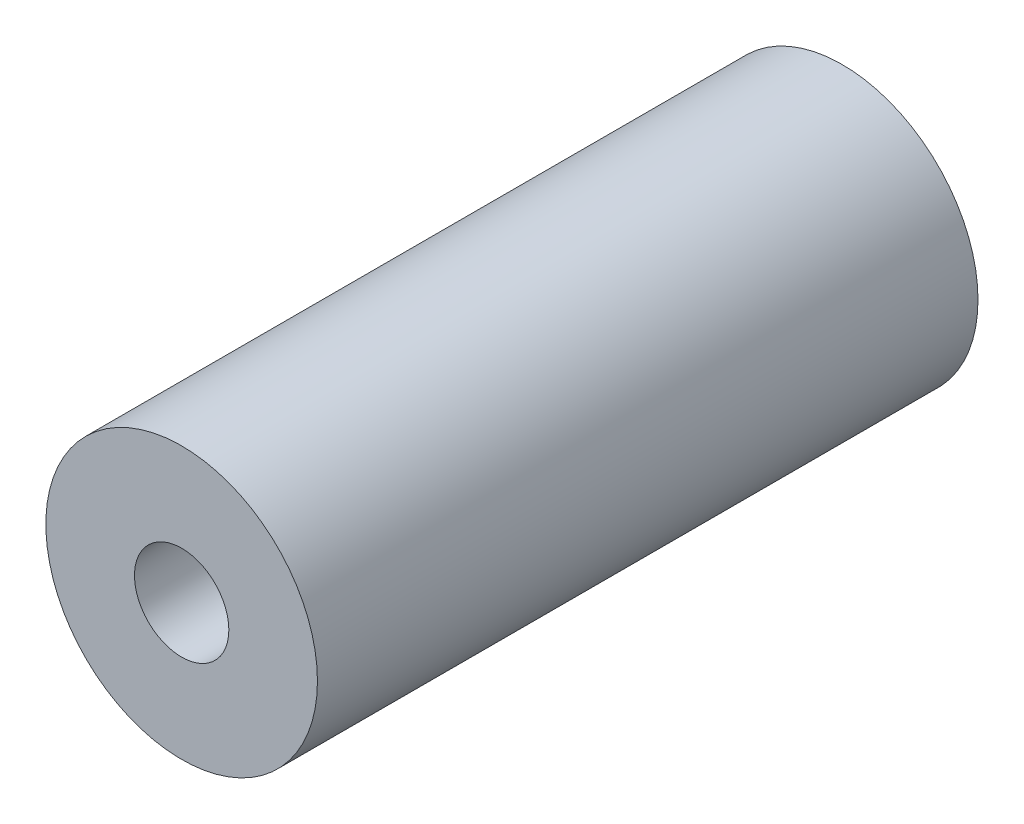
SolidWorks part; units mm, degrees
ref_plane "Front" through (0, 0, 0) normal (0, 0, 1) x (1, 0, 0)
ref_plane "Top" through (0, 0, 0) normal (0, 1, 0) x (1, 0, 0)
ref_plane "Right" through (0, 0, 0) normal (1, 0, 0) x (0, 0, -1)
sketch "support-front" plane through (0, 0, 0) normal (0, 0, 1) x (1, 0, 0)
  circle A0 centre (0, 0) radius 8.635
  circle A1 centre (0, 0) radius 3
  dimension "diam-rod" = 6
  dimension "diam-cylinder" = 17.27
sketch "support-right" plane through (0, 0, 0) normal (1, 0, 0) x (0, 0, -1)
  line L0 (0, 8.635) -> (0, -8.635) construction
  line L1 (0, 8.635) -> (42, 8.635)
  line L2 (0, 8.635) -> (0, -8.635)
  line L3 (0, -8.635) -> (42, -8.635)
  line L4 (42, 8.635) -> (42, -8.635)
  line L5 (0, 0) -> (42, 0) construction
  line L6 (10, 8.635) -> (10, -8.635) construction
  dimension "length-constant" = 32
  dimension "stroke" = 10
  dimension "length" = 42
ref_plane "ref-plane-front" through (0, 0, 0) normal (0, 0, 1) x (1, 0, 0)
ref_plane "ref-plane-end" through (0, 0, -42) normal (0, 0, 1) x (1, 0, 0)
ref_axis "ref-axis-center" through (0, 0, -42) along (0, 0, 1)
sketch "Sketch3" plane through (0, 0, 0) normal (0, 0, 1) x (1, 0, 0)
  circle A0 centre (0, 0) radius 8.635 construction
  circle A1 centre (0, 0) radius 8.635
extrude "body" add sketch "Sketch3" against normal up to surface (42 mm away) up to plane "ref-plane-end"
sketch "Sketch4" plane through (0, 0, 0) normal (0, 0, 1) x (1, 0, 0)
  circle A0 centre (0, 0) radius 3 construction
  circle A1 centre (0, 0) radius 3
extrude "cut-hole" cut sketch "Sketch4" against normal up to surface (42 mm away) up to plane "ref-plane-end"
